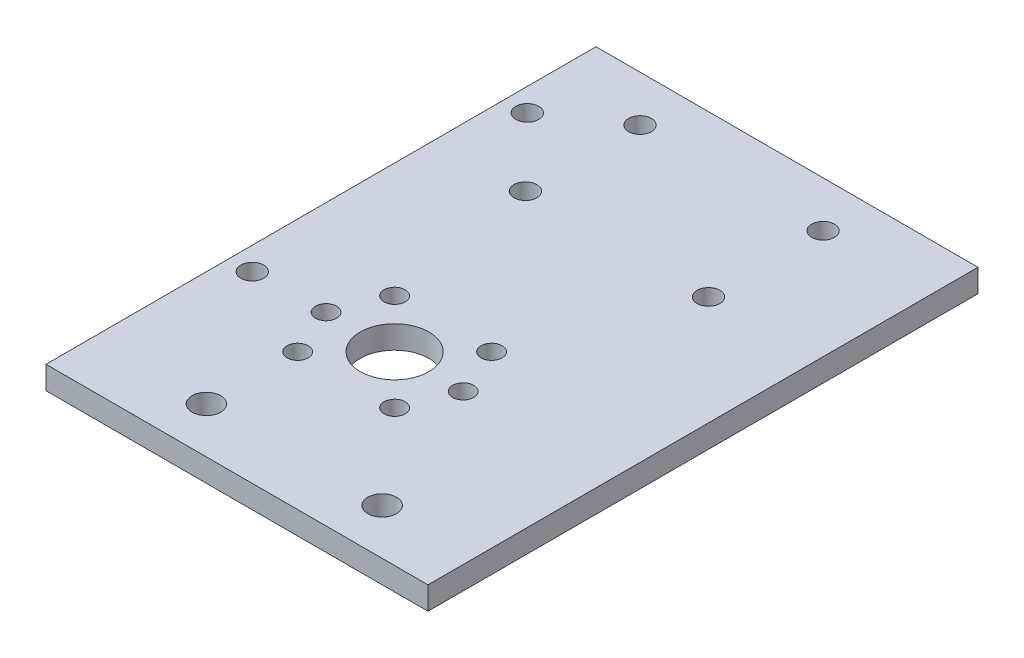
SolidWorks part; units mm, degrees
material "6061 Alloy"
ref_plane "Front Plane" through (0, 0, 0) normal (0, 0, 1) x (1, 0, 0)
ref_plane "Top Plane" through (0, 0, 0) normal (0, 1, 0) x (1, 0, 0)
ref_plane "Right Plane" through (0, 0, 0) normal (1, 0, 0) x (0, 0, -1)
sketch "Sketch1" plane through (0, 0, 0) normal (0, 1, 0) x (1, 0, 0)
  line L1 (-52.925, 76.2) -> (52.925, 76.2)
  line L2 (-52.925, 76.2) -> (-52.925, -76.2)
  line L3 (-52.925, -76.2) -> (52.925, -76.2)
  line L4 (52.925, 76.2) -> (52.925, -76.2)
  line L5 (-52.925, 76.2) -> (52.925, -76.2) construction
  line L6 (-52.925, -76.2) -> (52.925, 76.2) construction
  point P0 (0, 0)
  dimension "D1" = 152.4
  dimension "D2" = 105.85
extrude "Boss-Extrude1" add sketch "Sketch1" along normal blind 6.35
sketch "Sketch2" plane through (0, 6.35, 0) normal (0, 1, 0) x (1, 0, 0)
  line L0 (3.175, 0) -> (3.175, -11.2478) construction
  line L1 (0, 0) -> (-15.1024, 0) construction
  line L2 (-52.925, -76.2) -> (52.925, -76.2) construction
  line L3 (-52.925, 76.2) -> (-52.925, -76.2) construction
  line L4 (52.925, -76.2) -> (52.925, 76.2) construction
  line L6 (-52.925, 76.2) -> (-52.925, -76.2) construction
  line L7 (52.925, 76.2) -> (-52.925, 76.2) construction
  circle A0 centre (-21.175, -63.5) radius 3.9688
  circle A1 centre (27.525, -63.5) radius 3.9688
  circle A2 centre (-7.62, -24.911) radius 9.525
  circle A3 centre (-28.033, 63.5) radius 3.175
  circle A4 centre (-28.033, 31.75) radius 3.175
  circle A5 centre (22.699, 63.5) radius 3.175
  circle A6 centre (22.699, 31.75) radius 3.175
  circle A7 centre (-46.575, -25.4) radius 3.175
  circle A8 centre (-46.575, 50.8) radius 3.175
  dimension "D1" = 12.7
  dimension "D2" = 31.75
  dimension "D3" = 19.05
  dimension "D4" = 51.289
  dimension "D5" = 45.305
  dimension "D6" = 24.892
  dimension "D7" = 24.892
  dimension "D8" = 30.226
  dimension "D9" = 30.226
  dimension "D10" = 50.8
  dimension "D11" = 6.35
  dimension "D12" = 6.35
  dimension "D13" = 25.4
  dimension "D14" = 12.7
  dimension "D15" = 12.7
  dimension "D16" = 44.45
  dimension "D17" = 44.45
  dimension "D18" = 25.4
extrude "Cut-Extrude1" cut sketch "Sketch2" against normal up to next
sketch "Sketch3" plane through (0, 0, 0) normal (0, -1, 0) x (1, 0, 0)
  line L4 (52.925, -76.2) -> (52.925, 76.2)
  line L5 (52.925, 76.2) -> (-52.925, 76.2)
  line L6 (-52.925, 76.2) -> (-52.925, -76.2)
  line L7 (-52.925, -76.2) -> (52.925, -76.2)
  line L8 (52.925, -76.2) -> (52.925, 76.2)
  line L9 (52.925, 76.2) -> (-52.925, 76.2)
  line L10 (-52.925, 76.2) -> (-52.925, -76.2)
  line L11 (-52.925, -76.2) -> (52.925, -76.2)
  circle A1 centre (5.815, 38.346) radius 2.921
  circle A3 centre (11.38, 24.911) radius 2.921
  circle A5 centre (5.815, 11.476) radius 2.921
  circle A7 centre (-21.055, 38.346) radius 2.921
  circle A9 centre (-26.62, 24.911) radius 2.921
  circle A11 centre (-21.055, 11.476) radius 2.921
  dimension "D2" = 31.87
  dimension "D3" = 26.305
  dimension "D4" = 31.87
  dimension "D5" = 58.74
  dimension "D6" = 64.305
  dimension "D7" = 58.74
  dimension "D8" = 37.854
  dimension "D9" = 51.289
  dimension "D10" = 64.724
  dimension "D11" = 37.854
  dimension "D12" = 51.289
  dimension "D13" = 64.724
  dimension "D1" = 0
extrude "Cut-Extrude5" cut sketch "Sketch3" against normal up to next (6.35 mm away) flip side to cut
